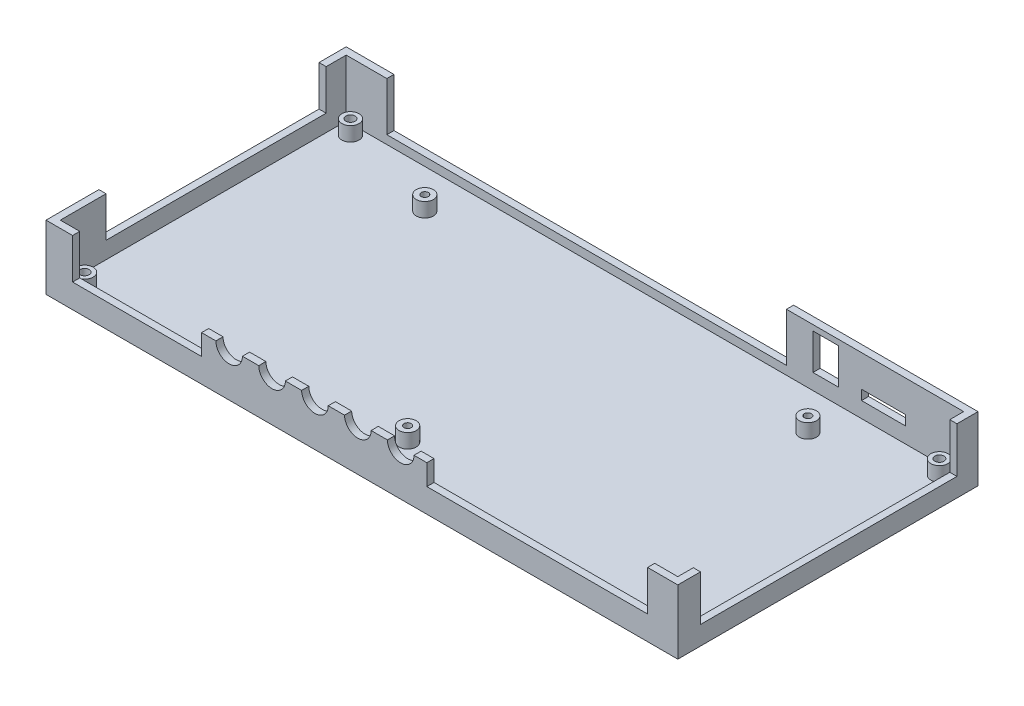
SolidWorks part; units mm, degrees
ref_plane "Front Plane" through (0, 0, 0) normal (0, 0, 1) x (1, 0, 0)
ref_plane "Top Plane" through (0, 0, 0) normal (0, 1, 0) x (1, 0, 0)
ref_plane "Right Plane" through (0, 0, 0) normal (1, 0, 0) x (0, 0, -1)
sketch "Sketch1" plane through (0, 0, 0) normal (0, 1, 0) x (1, 0, 0)
  line L0 (-110.5, -52.5) -> (-110.5, 52.5)
  line L1 (-108, -50) -> (108, -50)
  line L2 (-108, -50) -> (-108, 50)
  line L3 (-108, 50) -> (108, 50)
  line L4 (108, -50) -> (108, 50)
  line L5 (-108, -50) -> (108, 50) construction
  line L6 (-108, 50) -> (108, -50) construction
  line L7 (-110.5, 52.5) -> (110.5, 52.5)
  line L8 (110.5, -52.5) -> (110.5, 52.5)
  line L9 (-110.5, -52.5) -> (110.5, -52.5)
  point P0 (0, 0)
  dimension "D1" = 216
  dimension "D2" = 100
  dimension "D3" = 2.5
extrude "Boss-Extrude1" add sketch "Sketch1" along normal blind 20 contours L0 L9 L8 L7 L4 L1 L2 L3 region at (-108.0532, 0, 0)
extrude "Boss-Extrude2" add sketch "Sketch1<3>" against normal blind 2.5 contours L0 L7 L8 L9
sketch "Sketch1<3>" plane through (0, 0, 0) normal (0, 1, 0) x (1, 0, 0) same geometry as "Sketch1"
ref_plane "Plane1" through (-110.5, 20, 52.5) normal (1, 0, 0) x (0, 0, -1)
sketch "Sketch3" plane through (0, 0, 52.5) normal (0, 0, 1) x (1, 0, 0)
  line L0 (-110.5, 20) -> (110.5, 20) construction
  line L1 (-101.2008, 20) -> (99.9204, 20)
  line L2 (-101.2008, 20) -> (-101.2008, 5.8947)
  line L3 (-101.2008, 5.8947) -> (99.9204, 5.8947)
  line L4 (99.9204, 20) -> (99.9204, 5.8947)
extrude "Cut-Extrude1" cut sketch "Sketch3" against normal blind 10
sketch "Sketch4" plane through (110.5, 0, 0) normal (1, 0, 0) x (0, 0, -1)
  line L0 (-52.5, 20) -> (52.5, 20) construction
  line L1 (-44.5761, 20) -> (45.1289, 20)
  line L2 (-44.5761, 20) -> (-44.5761, 4.0461)
  line L3 (-44.5761, 4.0461) -> (45.1289, 4.0461)
  line L4 (45.1289, 20) -> (45.1289, 4.0461)
extrude "Cut-Extrude2" cut sketch "Sketch4" against normal blind 10
sketch "Sketch5" plane through (0, 0, 52.5) normal (0, 0, 1) x (1, 0, 0)
  line L0 (-144.165, 13.1347) -> (142.8743, 13.1347) construction
  line L1 (-101.2008, 5.8947) -> (99.9204, 5.8947) construction
  line L2 (0, -12.375) -> (0, 12.375) construction
  line L4 (-56.08, 5.8947) -> (22.72, 5.8947)
  line L6 (-41.78, 13.1347) -> (-36.08, 13.1347)
  line L7 (-26.78, 13.1347) -> (-21.08, 13.1347)
  line L8 (-11.78, 13.1347) -> (-6.08, 13.1347)
  line L9 (3.22, 13.1347) -> (8.92, 13.1347)
  line L10 (-56.08, 13.1347) -> (-56.08, 5.8947)
  line L11 (-56.08, 13.1347) -> (-51.08, 13.1347)
  line L12 (22.72, 13.1347) -> (22.72, 5.8947)
  line L13 (18.22, 13.1347) -> (22.72, 13.1347)
  circle A0 centre (-46.43, 13.1347) radius 4.65 construction
  circle A1 centre (-31.43, 13.1347) radius 4.65 construction
  circle A2 centre (-16.43, 13.1347) radius 4.65 construction
  circle A3 centre (-1.43, 13.1347) radius 4.65 construction
  circle A4 centre (13.57, 13.1347) radius 4.65 construction
  arc A5 (-51.08, 13.1347) -> (-41.78, 13.1347) centre (-46.43, 13.1347) ccw
  arc A6 (-36.08, 13.1347) -> (-26.78, 13.1347) centre (-31.43, 13.1347) ccw
  arc A7 (-21.08, 13.1347) -> (-11.78, 13.1347) centre (-16.43, 13.1347) ccw
  arc A8 (-6.08, 13.1347) -> (3.22, 13.1347) centre (-1.43, 13.1347) ccw
  arc A9 (8.92, 13.1347) -> (18.22, 13.1347) centre (13.57, 13.1347) ccw
  point P4 (-46.43, 13.1347)
  point P5 (-31.43, 13.1347)
  point P6 (-16.43, 13.1347)
  point P7 (-1.43, 13.1347)
  point P8 (13.57, 13.1347)
  dimension "D7" = 9.3
  dimension "D8" = 5
  dimension "D9" = 4.5
  dimension "D1" = 7.24
  dimension "D2" = 46.43
  dimension "D3" = 31.43
  dimension "D4" = 16.43
  dimension "D5" = 1.43
  dimension "D6" = 13.57
extrude "Boss-Extrude3" add sketch "Sketch5" against normal up to surface (2.5 mm away) up to face at (-0.3201, 11.4737, 50)
sketch "Sketch6" plane through (0, 0, -52.5) normal (0, 0, -1) x (-1, 0, 0)
  line L0 (110.5, 20) -> (-110.5, 20) construction
  line L1 (-46, 20) -> (46, 20)
  line L2 (-46, 20) -> (-46, 3)
  line L3 (-46, 3) -> (46, 3)
  line L4 (46, 20) -> (46, 3)
  line L5 (0, 12.375) -> (0, -12.375) construction
  dimension "D1" = 92
  dimension "D2" = 46
  dimension "D3" = 17
extrude "Cut-Extrude3" cut sketch "Sketch6" against normal blind 10
sketch "Sketch7" plane through (-110.5, 0, 0) normal (-1, 0, 0) x (0, 0, 1)
  line L0 (52.5, 20) -> (-52.5, 20) construction
  line L1 (34, 20) -> (-43, 20)
  line L2 (34, 20) -> (34, 5.9)
  line L3 (34, 5.9) -> (-43, 5.9)
  line L4 (-43, 20) -> (-43, 5.9)
  line L5 (52.5, 20) -> (52.5, -2.5) construction
  line L6 (52.5, -2.5) -> (-52.5, -2.5) construction
  dimension "D1" = 18.5
  dimension "D2" = 7
  dimension "D3" = 8.4
extrude "Cut-Extrude4" cut sketch "Sketch7" against normal blind 10
sketch "Sketch8" plane through (0, 0, -52.5) normal (0, 0, -1) x (-1, 0, 0)
  line L0 (110.5, 20) -> (46, 20) construction
  line L1 (45.2316, 20) -> (93.7751, 20)
  line L2 (45.2316, 20) -> (45.2316, 3)
  line L3 (45.2316, 3) -> (93.7751, 3)
  line L4 (93.7751, 20) -> (93.7751, 3)
  line L5 (-46, 3) -> (46, 3) construction
extrude "Cut-Extrude5" cut sketch "Sketch8" against normal blind 4
sketch "Sketch9" plane through (0, 0, -50) normal (0, 0, 1) x (1, 0, 0)
  line L1 (72.2471, 8.9082) -> (87.6268, 8.9082)
  line L2 (72.2471, 8.9082) -> (72.2471, 5.4667)
  line L3 (72.2471, 5.4667) -> (87.6268, 5.4667)
  line L4 (87.6268, 8.9082) -> (87.6268, 5.4667)
extrude "Cut-Extrude6" cut sketch "Sketch9" against normal blind 4
sketch "Sketch10" plane through (0, 0, -50) normal (0, 0, 1) x (1, 0, 0)
  line L1 (55.2825, 18.0604) -> (64.1512, 18.0604)
  line L2 (55.2825, 18.0604) -> (55.2825, 5.4968)
  line L3 (55.2825, 5.4968) -> (64.1512, 5.4968)
  line L4 (64.1512, 18.0604) -> (64.1512, 5.4968)
extrude "Cut-Extrude7" cut sketch "Sketch10" against normal blind 4
sketch "Sketch11" plane through (0, -2.5, 0) normal (0, -1, 0) x (1, 0, 0)
  line L0 (0, -12.375) -> (0, 12.375) construction
  line L1 (-103, 46.5) -> (103, 46.5)
  line L2 (-103, 46.5) -> (-103, -46.5)
  line L3 (-103, -46.5) -> (103, -46.5)
  line L4 (103, 46.5) -> (103, -46.5)
  dimension "D1" = 206
  dimension "D2" = 93
  dimension "D3" = 103
  dimension "D4" = 46.5
sketch "Sketch15" plane through (0, 0, 0) normal (0, 1, 0) x (1, 0, 0)
  line L0 (-103, -46.5) -> (103, -46.5) construction
  line L1 (103, -46.5) -> (103, 46.5) construction
  line L2 (-103, 46.5) -> (103, 46.5) construction
  line L3 (-103, -46.5) -> (-103, 46.5) construction
  line L4 (-103, -46.5) -> (103, -46.5)
  line L5 (103, -46.5) -> (103, 46.5)
  line L6 (-103, 46.5) -> (103, 46.5)
  line L7 (-103, -46.5) -> (-103, 46.5)
  circle A0 centre (-103, 46.5) radius 3
  circle A1 centre (103, 46.5) radius 3
  circle A2 centre (103, -46.5) radius 3
  circle A4 centre (-103, -46.5) radius 3
  dimension "D1" = 6
extrude "Boss-Extrude4" add sketch "Sketch15" along normal blind 5 contours L6 A0 L7 | L7 A0 L6 | L7 A4 L4 | L4 A4 L7 | L4 A2 L5 | L5 A2 L4 | L5 A1 L6 | L6 A1 L5 region at (-101.7268, 0, 45.2268) region at (-103.4244, 0, 46.9244) region at (101.7268, 0, 45.2268) region at (103.4244, 0, 46.9244) region at (-103.4244, 0, -46.9244) region at (-101.7268, 0, -45.2268) region at (101.7268, 0, -45.2268) region at (103.4244, 0, -46.9244)
hole_wizard "CBORE for M3 Hex Head Cap Screw1" positions "Sketch12" profile "Sketch14" counterbore size "M3" standard "ISO"
sketch "Sketch12" plane through (0, -2.5, 0) normal (0, -1, 0) x (-1, 0, 0)
  point P0 (103, -46.5)
  point P3 (-103, -46.5)
  point P6 (-103, 46.5)
  point P9 (103, 46.5)
sketch "Sketch14" plane through (-103, -2.5, 46.5) normal (1, 0, 0) x (0, 0, -1)
  line L0 (0, 0) -> (0, 11.0614)
  line L1 (0, 11.0614) -> (1.6, 10.1)
  line L2 (1.6, 10.1) -> (1.6, 2.5)
  line L3 (1.6, 2.5) -> (2.75, 2.5)
  line L4 (2.75, 2.5) -> (2.75, 0)
  line L5 (2.75, 0) -> (0, 0)
  line L10 (0, 11.0614) -> (-1.6, 10.1) construction
  line L11 (0, -6.35) -> (0, 107.95) construction
  dimension "Hole Dia." = 3.2
  dimension "Hole Depth" = 10.1
  dimension "C'Bore Dia." = 5.5
  dimension "C'Bore Depth" = 2.5
  dimension "Drill Angle" = 118
sketch "Sketch17" plane through (0, 0, 0) normal (0, 1, 0) x (1, 0, 0)
  line L0 (-67, 36.5) -> (67, 36.5) construction
  line L2 (0, -12.375) -> (0, 12.375) construction
  circle A0 centre (-67, 36.5) radius 3
  circle A1 centre (67, 36.5) radius 3
  circle A2 centre (0, -36.5) radius 3
  circle A3 centre (-103, 46.5) radius 1.6 construction
  circle A4 centre (103, 46.5) radius 3 construction
  circle A5 centre (-103, 46.5) radius 3 construction
  circle A6 centre (-103, -46.5) radius 3 construction
  point P2 (0, -36.5)
  point P5 (0, 0)
  point P8 (0, 0)
  dimension "D5" = 6
  dimension "D1" = 36
  dimension "D2" = 36
  dimension "D3" = 10
  dimension "D4" = 10
  dimension "D6" = 10
  dimension "D7" = 103
extrude "Boss-Extrude5" add sketch "Sketch17" along normal up to surface (5 mm away) up to face at (-103, 5, -44.9)
hole_wizard "M3 Tapped Hole1" positions "Sketch18" profile "Sketch19" tap size "M3" standard "ISO"
sketch "Sketch18" plane through (0, 5, 0) normal (0, 1, 0) x (1, 0, 0)
  point P0 (-67, 36.5)
  point P3 (67, 36.5)
  point P6 (0, -36.5)
sketch "Sketch19" plane through (-67, 5, -36.5) normal (1, 0, 0) x (0, 0, 1)
  line L0 (0, 0) -> (0, 5.7511)
  line L1 (0, 5.7511) -> (1.25, 5)
  line L2 (1.25, 5) -> (1.25, 0)
  line L5 (1.25, 0) -> (0, 0)
  line L10 (0, 5.7511) -> (-1.25, 5) construction
  line L11 (0, -6.35) -> (0, 107.95) construction
  dimension "Tap Drill Dia." = 2.5
  dimension "Tap Drill Depth" = 5
  dimension "Drill Angle" = 118
cosmetic thread "Hole Thread1" parameters "D1"=6, "D2"=3
cosmetic thread "Hole Thread2" parameters "D1"=6, "D2"=3
cosmetic thread "Hole Thread3" parameters "D1"=6, "D2"=3
equation "\"D2@Sketch6\"=\"D1@Sketch6\"/2"
equation "\"D3@Sketch11\"=\"D1@Sketch11\"/2"
equation "\"D4@Sketch11\"=\"D2@Sketch11\"/2"
